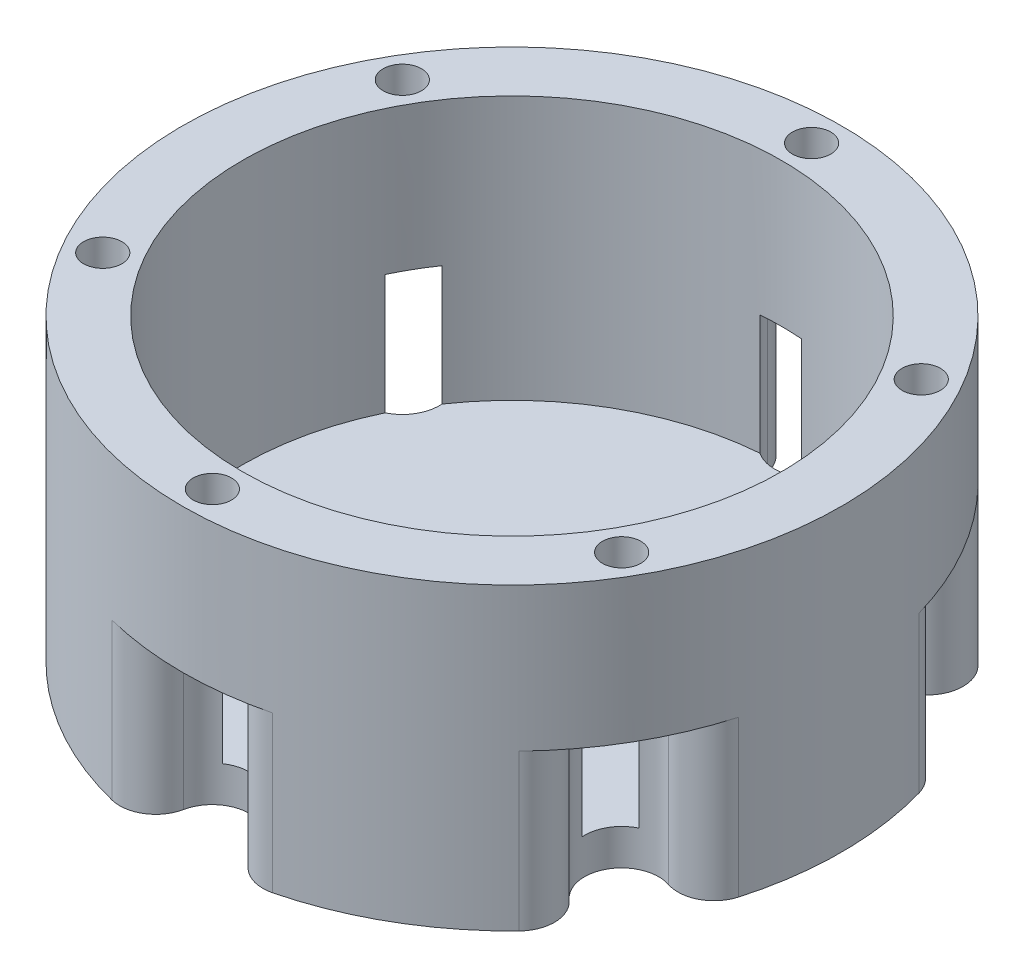
SolidWorks part; units mm, degrees
ref_plane "Front Plane" through (0, 0, 0) normal (0, 0, 1) x (1, 0, 0)
ref_plane "Top Plane" through (0, 0, 0) normal (0, 1, 0) x (1, 0, 0)
ref_plane "Right Plane" through (0, 0, 0) normal (1, 0, 0) x (0, 0, -1)
sketch "Sketch1" plane through (0, 0, 0) normal (0, 1, 0) x (1, 0, 0)
  circle A0 centre (0, 0) radius 27.5
  circle A1 centre (0, 0) radius 25 construction
  circle A2 centre (0, 25) radius 1.6
  circle A3 centre (21.6506, 12.5) radius 1.6
  circle A4 centre (21.6506, -12.5) radius 1.6
  circle A5 centre (0, -25) radius 1.6
  circle A6 centre (-21.6506, -12.5) radius 1.6
  circle A7 centre (-21.6506, 12.5) radius 1.6
  point P19 (0, 0)
  point P31 (0, 0)
  dimension "D1" = 55
  dimension "D2" = 50
  dimension "D3" = 3.2
  dimension "D4" = 6
extrude "Boss-Extrude1" add sketch "Sketch1" along normal blind 25
sketch "Sketch2" plane through (0, 25, 0) normal (0, 1, 0) x (1, 0, 0)
  circle A0 centre (0, 0) radius 22.5
  dimension "D1" = 45
extrude "Cut-Extrude1" cut sketch "Sketch2" against normal blind 22
sketch "Sketch3" plane through (0, 0, 0) normal (0, -1, 0) x (1, 0, 0)
  circle A0 centre (0, 25) radius 3.1
  dimension "D1" = 6.2
extrude "Cut-Extrude2" cut sketch "Sketch3" against normal blind 13
fillet "Fillet1" radius 3 2 edges at (-1.9213, 6.5, 27.4328) (1.9213, 6.5, 27.4328)
pattern_circular "CirPattern1" count 6 over 360 about axis through (0, 25, 0) along (0, -1, 0) of "Cut-Extrude2", "Fillet1" reverse direction yes
